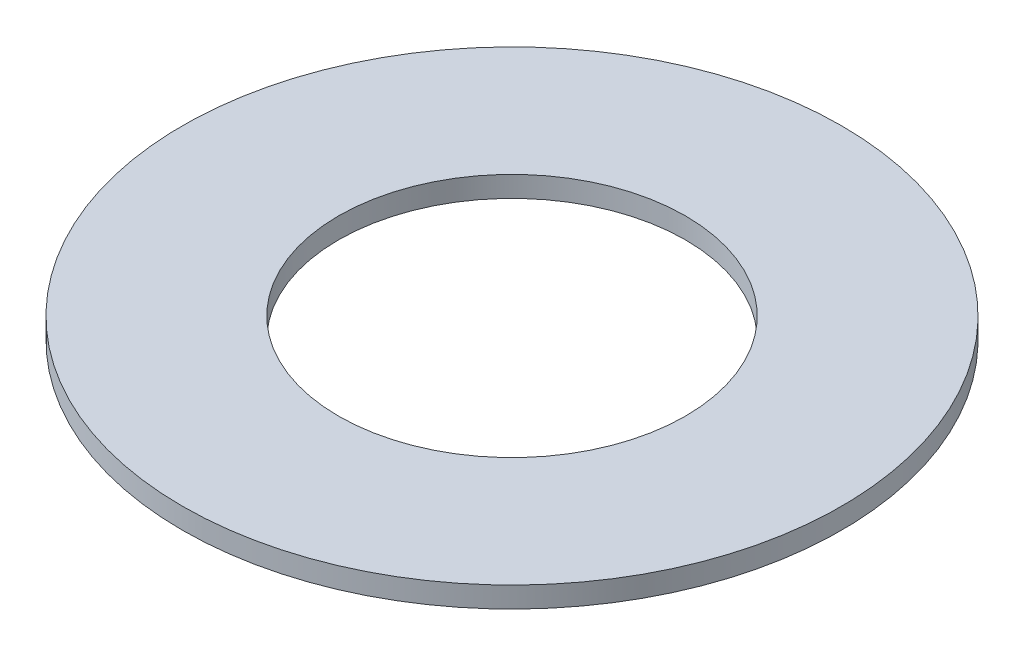
SolidWorks part; units mm, degrees
ref_plane "Front Plane" through (0, 0, 0) normal (0, 0, 1) x (1, 0, 0)
ref_plane "Top Plane" through (0, 0, 0) normal (0, 1, 0) x (1, 0, 0)
ref_plane "Right Plane" through (0, 0, 0) normal (1, 0, 0) x (0, 0, -1)
sketch "Sketch1" plane through (0, 0, 0) normal (0, 1, 0) x (1, 0, 0)
  circle A0 centre (0, 0) radius 95
  dimension "FLANGE_OD" = 190
extrude "Boss-Extrude1" add sketch "Sketch1" along normal blind 6
sketch "Sketch2" plane through (0, 0, 0) normal (0, 1, 0) x (1, 0, 0)
  circle A0 centre (0, 0) radius 50
  dimension "BORE_D" = 100
extrude "Cut-Extrude1" cut sketch "Sketch2" along normal through all
sketch "Sketch3" plane through (0, 6, 0) normal (0, 1, 0) x (1, 0, 0)
  circle A0 centre (0, 0) radius 41.5057 construction
  circle A1 centre (-41.5057, 0) radius 5.7368
  dimension "BOLT_D" = 11.4737
  dimension "BOLT_PCD" = 83.0115
extrude "Cut-Extrude2" cut sketch "Sketch3" against normal blind 4.4979 rebuild error yes
pattern_circular "CirPattern1" count 6 over 360 rebuild error yes
